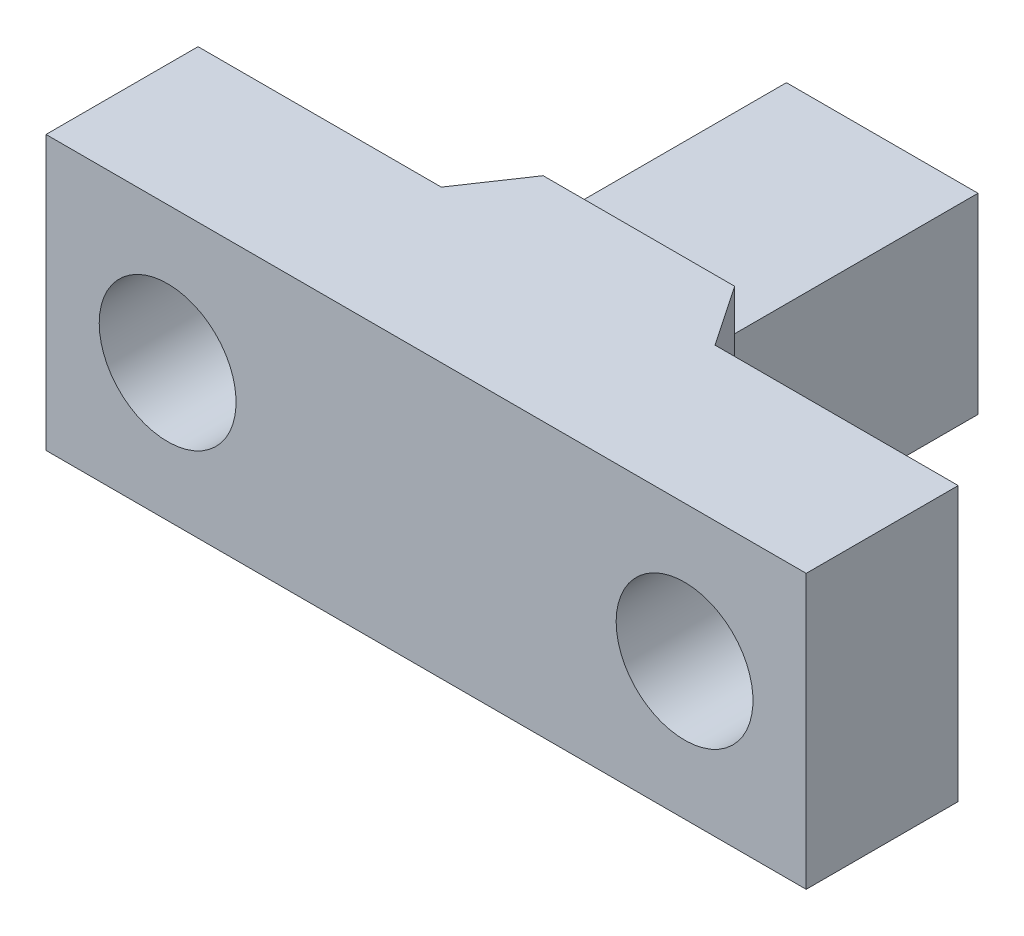
SolidWorks part; units mm, degrees
ref_plane "Plano frontal" through (0, 0, 0) normal (0, 0, 1) x (1, 0, 0)
ref_plane "Plano superior" through (0, 0, 0) normal (0, 1, 0) x (1, 0, 0)
ref_plane "Plano direito" through (0, 0, 0) normal (1, 0, 0) x (0, 0, -1)
sketch "Esboço1" plane through (0, 0, 0) normal (0, 1, 0) x (1, 0, 0)
  line L0 (0, 0) -> (25, 0)
  line L1 (25, 0) -> (25, 5)
  line L2 (25, 5) -> (17, 5)
  line L3 (17, 5) -> (17, 15)
  line L5 (8, 15) -> (8, 5)
  line L6 (8, 5) -> (0, 5)
  line L7 (0, 5) -> (0, 0)
  line L13 (12.5, 15) -> (12.5, 0) construction
  line L14 (8, 15) -> (17, 15)
  point P11 (12.5, 15)
  dimension "D2" = 9
  dimension "D3" = 5
  dimension "D4" = 25
  dimension "D6" = 10
extrude "Ressalto-extrusão1" add sketch "Esboço1" along normal blind 9
sketch "Esboço2" plane through (0, 0, -15) normal (0, 0, -1) x (-1, 0, 0)
  line L0 (-17, 4.5) -> (-8, 4.5) construction
  line L1 (-17, 9) -> (-8, 9)
  line L2 (-17, 9) -> (-17, 0)
  line L3 (-17, 0) -> (-8, 0)
  line L4 (-8, 9) -> (-8, 0)
  line L5 (-15.65, 7.65) -> (-9.35, 7.65)
  line L6 (-15.65, 7.65) -> (-15.65, 1.35)
  line L7 (-15.65, 1.35) -> (-9.35, 1.35)
  line L8 (-9.35, 7.65) -> (-9.35, 1.35)
  line L9 (-12.5, 9) -> (-12.5, 0) construction
  line L10 (-17, 9) -> (-8, 9) construction
  point P14 (-12.5, 7.65)
  point P15 (-9.35, 4.5)
  dimension "D1" = 6.3
  dimension "D2" = 6.3
  dimension "D3" = 1.35
extrude "Corte-extrusão1" cut sketch "Esboço2" against normal blind 8
sketch "Esboço3" plane through (0, 0, -5) normal (0, 0, -1) x (-1, 0, 0)
  line L0 (-25, 4.5) -> (0, 4.5) construction
  line L1 (-25, 9) -> (-25, 0) construction
  line L2 (0, 9) -> (0, 0) construction
  circle A0 centre (-4, 4.5) radius 2.25
  circle A1 centre (-21, 4.5) radius 2.25
  dimension "D1" = 4.5
  dimension "D2" = 4.5
  dimension "D3" = 4
  dimension "D4" = 4
  dimension "D5" = 17
extrude "Corte-extrusão2" cut sketch "Esboço3" against normal through all
chamfer "Chanfro2" distance 2 distance2 1.35 2 edges at (8, 4.5, -7) (17, 4.5, -7) first distance on face at (8, 4.5, -6) first distance on face at (17, 4.5, -6)
